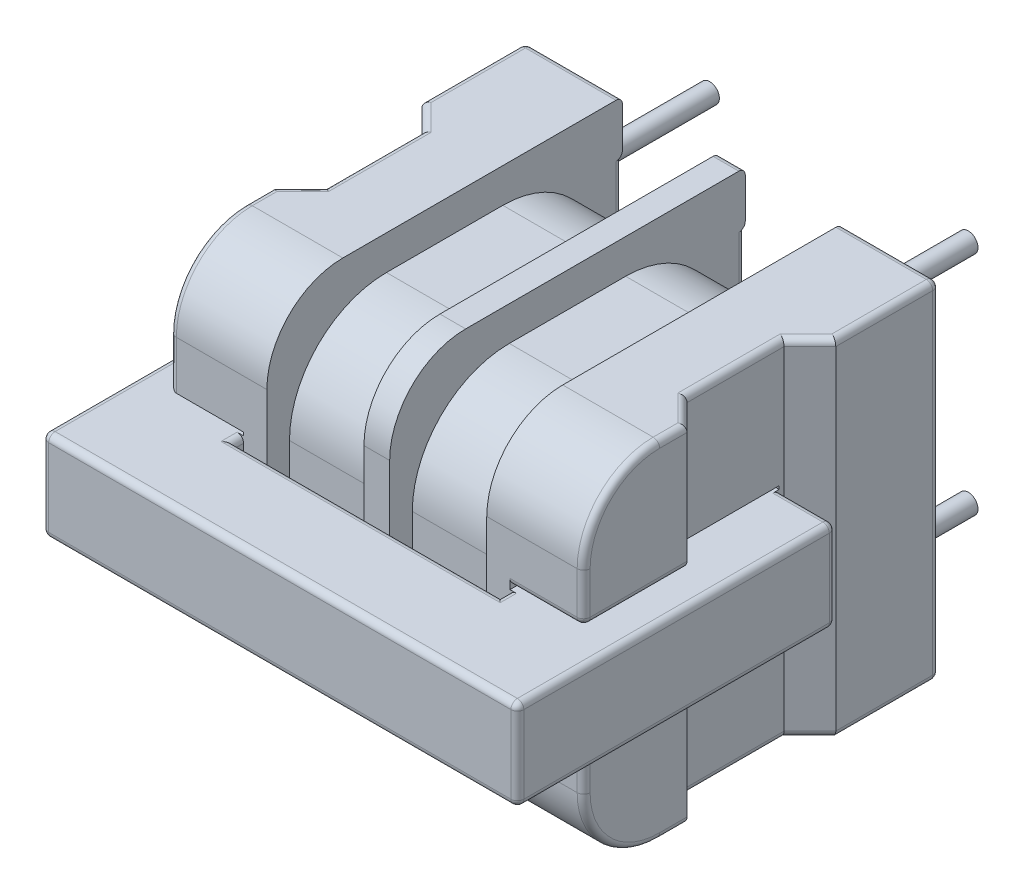
SolidWorks part; units mm, degrees
material "C (Graphite)"
ref_plane "Front Plane" through (0, 0, 0) normal (0, 0, 1) x (1, 0, 0)
ref_plane "Top Plane" through (0, 0, 0) normal (0, 1, 0) x (1, 0, 0)
ref_plane "Right Plane" through (0, 0, 0) normal (1, 0, 0) x (0, 0, -1)
sketch "Sketch1" plane through (0, 0, 0) normal (0, 0, 1) x (1, 0, 0)
  line L1 (-7.35, 5.35) -> (7.35, 5.35)
  line L2 (-7.35, 5.35) -> (-7.35, -5.35)
  line L3 (-7.35, -5.35) -> (7.35, -5.35)
  line L4 (7.35, 5.35) -> (7.35, -5.35)
  line L5 (-7.35, 5.35) -> (7.35, -5.35) construction
  line L6 (-7.35, -5.35) -> (7.35, 5.35) construction
  point P0 (0, 0)
  dimension "D1" = 10.7
  dimension "D2" = 14.7
extrude "Boss-Extrude1" add sketch "Sketch1" along normal blind 14
sketch "Sketch2" plane through (0, 0, 0) normal (1, 0, 0) x (0, 0, -1)
  line L0 (-5.5, 0) -> (0, 0) construction
  line L1 (-7, 4.5) -> (-4, 4.5)
  line L2 (-10, 1.5) -> (-10, -1.5)
  line L3 (-7, -4.5) -> (-4, -4.5)
  line L4 (-1, 1.5) -> (-1, -1.5)
  line L5 (-10, 4.5) -> (-1, -4.5) construction
  line L6 (-10, -4.5) -> (-1, 4.5) construction
  arc A0 (-10, -1.5) -> (-7, -4.5) centre (-7, -1.5) ccw
  arc A1 (-4, -4.5) -> (-1, -1.5) centre (-4, -1.5) ccw
  arc A2 (-4, 4.5) -> (-1, 1.5) centre (-4, 1.5) cw
  arc A3 (-7, 4.5) -> (-10, 1.5) centre (-7, 1.5) ccw
  point P0 (-5.5, 0)
  dimension "D1" = 3
  dimension "D3" = 5.5
  dimension "D2" = 9
sketch "Sketch3" plane through (0, 0, 0) normal (0, 1, 0) x (1, 0, 0)
  line L0 (-0.4, -10.8) -> (0.4, -10.8) construction
  line L1 (-3.4, -10.3) -> (-0.4, -10.3)
  line L2 (-3.4, -10.3) -> (-3.4, -11.3)
  line L3 (-3.4, -11.3) -> (-0.4, -11.3)
  line L4 (-0.4, -10.3) -> (-0.4, -11.3)
  line L5 (-3.4, -10.3) -> (-0.4, -11.3) construction
  line L6 (-3.4, -11.3) -> (-0.4, -10.3) construction
  line L7 (0.4, -10.3) -> (3.4, -10.3)
  line L8 (0.4, -10.3) -> (0.4, -11.3)
  line L9 (0.4, -11.3) -> (3.4, -11.3)
  line L10 (3.4, -10.3) -> (3.4, -11.3)
  line L11 (0.4, -10.3) -> (3.4, -11.3) construction
  line L12 (0.4, -11.3) -> (3.4, -10.3) construction
  line L13 (0, -10.382) -> (0, -10.8) construction
  line L14 (0, -10) -> (0, -1) construction
  line L17 (7.35, -14) -> (-7.35, -14) construction
  point P0 (-1.9, -10.8)
  point P5 (1.9, -10.8)
  dimension "D1" = 3
  dimension "D2" = 0.8
  dimension "D3" = 2.7
  dimension "D4" = 1
sweep "Cut-Sweep1" cut profiles "Sketch3" path "Sketch2"
sketch "Sketch4" plane through (0, 0, 0) normal (0, 0, 1) x (1, 0, 0)
  line L0 (7.35, -5.35) -> (7.35, 5.35) construction
  line L1 (-7.35, 5.35) -> (7.35, 5.35)
  line L2 (-7.35, 5.35) -> (-7.35, 1.4)
  line L3 (-7.35, 1.4) -> (7.35, 1.4)
  line L4 (7.35, 5.35) -> (7.35, 1.4)
  line L6 (-7.35, -5.35) -> (7.35, -5.35)
  line L7 (-7.35, -5.35) -> (-7.35, -1.4)
  line L8 (-7.35, -1.4) -> (7.35, -1.4)
  line L9 (7.35, -5.35) -> (7.35, -1.4)
  dimension "D1" = 2.8
extrude "Cut-Extrude1" cut sketch "Sketch4" against normal blind 3 from surface at 14 starting at face at (0, 0, 14)
fillet "Fillet1" radius 2.35 2 edges at (0, -5.35, 11) (0, 5.35, 11)
fillet "Fillet2" radius 0.2 12 edges at (-3.4, 0, 0) (-1.9, -3.078, 0) (-1.9, 3.078, 0) (-0.4, 0, 0) (0, -5.35, 0) (-7.35, 0, 0) (0, 5.35, 0) (7.35, 0, 0) (0.4, 0, 0) (1.9, -3.078, 0) (1.9, 3.078, 0) (3.4, 0, 0)
sketch "Sketch5" plane through (0, 0, 0) normal (0, 0, 1) x (1, 0, 0)
  line L0 (-3.4, 3.8033) -> (-3.4, 5.35) construction
  line L1 (-3.4, 4.2849) -> (-0.3962, 4.2849)
  line L2 (-3.4, 4.2849) -> (-3.4, 5.7963)
  line L3 (-3.4, 5.7963) -> (-0.3962, 5.7963)
  line L4 (-0.3962, 4.2849) -> (-0.3962, 5.7963)
  line L5 (0.4, 3.8033) -> (0.4, 5.35) construction
  line L6 (0.4, 4.2849) -> (3.4038, 4.2849)
  line L7 (0.4, 4.2849) -> (0.4, 5.7963)
  line L8 (0.4, 5.7963) -> (3.4038, 5.7963)
  line L9 (3.4038, 4.2849) -> (3.4038, 5.7963)
  line L10 (-3.4, -5.35) -> (-3.4, -3.8033) construction
  line L11 (-3.4, -4.418) -> (-0.3962, -4.418)
  line L12 (-3.4, -4.418) -> (-3.4, -6.0458)
  line L13 (-3.4, -6.0458) -> (-0.3962, -6.0458)
  line L14 (-0.3962, -4.418) -> (-0.3962, -6.0458)
  line L15 (-3.4, -4.8) -> (-3.4, -1.5) construction
  line L16 (0.4, -5.35) -> (0.4, -3.8033) construction
  line L17 (0.4, -4.418) -> (3.4038, -4.418)
  line L18 (0.4, -4.418) -> (0.4, -6.0458)
  line L19 (0.4, -6.0458) -> (3.4038, -6.0458)
  line L20 (3.4038, -4.418) -> (3.4038, -6.0458)
  line L21 (7.35, 1.4) -> (-7.35, 1.4) construction
  line L22 (-7.35, 5.35) -> (-6.4, 5.35)
  line L23 (-7.35, 5.35) -> (-7.35, 1.4)
  line L24 (-7.35, 1.4) -> (-6.4, 1.4)
  line L25 (-6.4, 5.35) -> (-6.4, 1.4)
  line L26 (-7.35, -5.35) -> (-6.4, -5.35)
  line L27 (-7.35, -5.35) -> (-7.35, -1.4)
  line L28 (-7.35, -1.4) -> (-6.4, -1.4)
  line L29 (-6.4, -5.35) -> (-6.4, -1.4)
  line L30 (7.35, 5.35) -> (6.4, 5.35)
  line L31 (7.35, 5.35) -> (7.35, 1.4)
  line L32 (7.35, 1.4) -> (6.4, 1.4)
  line L33 (6.4, 5.35) -> (6.4, 1.4)
  line L34 (7.35, -5.35) -> (6.4, -5.35)
  line L35 (7.35, -5.35) -> (7.35, -1.4)
  line L36 (7.35, -1.4) -> (6.4, -1.4)
  line L37 (6.4, -5.35) -> (6.4, -1.4)
  dimension "D1" = 12.8
extrude "Cut-Extrude2" cut sketch "Sketch5" along normal through all
sketch "Sketch6" plane through (0, 0, 0) normal (0, 0, 1) x (1, 0, 0)
  line L0 (0.4, -4.418) -> (0.4, -1.5) construction
  line L1 (-3.4, 5.35) -> (-0.4, 5.35)
  line L2 (-3.4, 5.35) -> (-3.4, 3)
  line L3 (-3.4, 3) -> (-0.4, 3)
  line L4 (-0.4, 5.35) -> (-0.4, 3)
  line L5 (0.4, 3) -> (3.4038, 3)
  line L6 (0.4, 3) -> (0.4, 5.35)
  line L7 (0.4, 5.35) -> (3.4038, 5.35)
  line L8 (3.4038, 3) -> (3.4038, 5.35)
  line L9 (-3.4, -5.35) -> (-0.4, -5.35)
  line L10 (-3.4, -5.35) -> (-3.4, -3)
  line L11 (-3.4, -3) -> (-0.4, -3)
  line L12 (-0.4, -5.35) -> (-0.4, -3)
  line L13 (0.4, -2.959) -> (3.4038, -2.959)
  line L14 (0.4, -2.959) -> (0.4, -5.35)
  line L15 (0.4, -5.35) -> (3.4038, -5.35)
  line L16 (3.4038, -2.959) -> (3.4038, -5.35)
extrude "Cut-Extrude3" cut sketch "Sketch6" along normal blind 1
sketch "Sketch7" plane through (0, 0, 0) normal (0, 0, 1) x (1, 0, 0)
  line L1 (-3.4, 3) -> (-0.3962, 3)
  line L2 (-3.4, 3) -> (-3.4, 5.35)
  line L3 (-3.4, 5.35) -> (-0.3962, 5.35)
  line L4 (-0.3962, 3) -> (-0.3962, 5.35)
  line L5 (0.4, 3) -> (3.4038, 3)
  line L6 (0.4, 3) -> (0.4, 5.35)
  line L7 (0.4, 5.35) -> (3.4038, 5.35)
  line L8 (3.4038, 3) -> (3.4038, 5.35)
  line L9 (-3.4, -3) -> (-0.3962, -3)
  line L10 (-3.4, -3) -> (-3.4, -5.35)
  line L11 (-3.4, -5.35) -> (-0.3962, -5.35)
  line L12 (-0.3962, -3) -> (-0.3962, -5.35)
  line L13 (0.4, -3) -> (3.4038, -3)
  line L14 (0.4, -3) -> (0.4, -5.35)
  line L15 (0.4, -5.35) -> (3.4038, -5.35)
  line L16 (3.4038, -3) -> (3.4038, -5.35)
extrude "Cut-Extrude4" cut sketch "Sketch7" against normal blind 1 from vertex
sketch "Sketch8" plane through (0, 0, 0) normal (0, 1, 0) x (1, 0, 0)
  line L0 (-6.4, -3.2) -> (-5.6, -4)
  line L1 (-6.4, -11) -> (-6.4, 0) construction
  line L2 (-5.6, -4) -> (-5.6, -7)
  line L3 (-5.6, -7) -> (-6.4, -7.8)
  line L4 (-6.4, -7.8) -> (-6.4, -3.2)
  line L5 (6.4, -3.2) -> (6.4, -7.8)
  line L6 (6.4, -8.65) -> (6.4, -0.2) construction
  line L7 (6.4, -7.8) -> (5.6, -7)
  line L8 (5.6, -7) -> (5.6, -4)
  line L9 (5.6, -4) -> (6.4, -3.2)
  line L10 (-5.6, -5.5) -> (-3.4, -5.5) construction
  line L11 (-3.4, -8.7704) -> (-3.4, -2.2296) construction
  line L13 (-3.4, -5.5) -> (5.6, -5.5) construction
  point P16 (-5.6, -5.5)
  dimension "D1" = 4.6
  dimension "D2" = 3
extrude "Cut-Extrude5" cut sketch "Sketch8" along normal through all from vertex
sketch "Sketch9" plane through (0, 0, 0) normal (0, 1, 0) x (1, 0, 0)
  line L0 (-6.4, -3.2) -> (-5.6, -4)
  line L1 (-5.6, -4) -> (-5.6, -7)
  line L2 (-5.6, -7) -> (-6.4, -7.8)
  line L3 (-6.4, -7.8) -> (-6.4, -3.2)
  line L4 (6.4, -3.2) -> (5.6, -4)
  line L5 (5.6, -4) -> (5.6, -7)
  line L6 (5.6, -7) -> (6.4, -7.8)
  line L7 (6.4, -7.8) -> (6.4, -3.2)
extrude "Cut-Extrude6" cut sketch "Sketch9" against normal through all from vertex
sketch "Sketch10" plane through (0, 0, 0) normal (0, 1, 0) x (1, 0, 0)
  line L0 (-3.4, -11) -> (-6.4, -11) construction
  line L1 (-4.12, -11) -> (4.12, -11)
  line L2 (-4.12, -11) -> (-4.12, -11.3)
  line L3 (-4.12, -11.3) -> (4.12, -11.3)
  line L4 (4.12, -11) -> (4.12, -11.3)
  line L5 (6.4, -11) -> (3.4, -11) construction
  line L6 (-0.4, -11.3) -> (-3.4, -11.3) construction
  line L7 (-4.12, -11) -> (-6.4, -11) construction
  line L8 (4.12, -11) -> (6.4, -11) construction
  line L9 (-6.4, 0) -> (-6.4, -3.2)
  line L10 (-6.4, -3.2) -> (-5.6, -4)
  line L11 (-5.6, -4) -> (-5.6, -4.15)
  line L12 (-5.6, -7) -> (-5.6, -4) construction
  line L13 (-5.6, -4.15) -> (-7.35, -4.15)
  line L14 (-7.35, -0.2) -> (-7.35, -14) construction
  line L15 (-7.35, -4.15) -> (-7.35, 0)
  line L16 (-7.35, 0) -> (-6.4, 0)
  line L17 (6.4, 0) -> (6.4, -3.2)
  line L18 (6.4, -3.2) -> (5.6, -4)
  line L19 (5.6, -4) -> (5.6, -4.15)
  line L20 (5.6, -4) -> (5.6, -7) construction
  line L21 (5.6, -4.15) -> (7.35, -4.15)
  line L22 (7.35, -0.2) -> (7.35, -14) construction
  line L23 (7.35, -4.15) -> (7.35, 0)
  line L24 (7.35, 0) -> (6.4, 0)
  line L25 (-5.6, -7) -> (-5.6, -6.85) construction
  line L26 (-5.6, -6.85) -> (-5.6, -4.15) construction
  line L27 (5.6, -7) -> (5.6, -6.85) construction
  line L28 (5.6, -4) -> (5.6, -7) construction
  line L29 (5.6, -6.85) -> (5.6, -4.15) construction
  dimension "D1" = 8.24
  dimension "D2" = 2.7
extrude "Cut-Extrude7" cut sketch "Sketch10" against normal through all and the other way through all
sketch "Sketch11" plane through (0, 0, 0) normal (0, 0, 1) x (1, 0, 0)
  line L0 (-4.12, -1.4) -> (-4.12, 1.4) construction
  line L1 (-7.35, 1.4) -> (-4.12, 1.4)
  line L2 (-7.35, 1.4) -> (-7.35, 1.5)
  line L3 (-7.35, 1.5) -> (-4.12, 1.5)
  line L4 (-4.12, 1.4) -> (-4.12, 1.5)
  line L5 (-7.35, -1.4) -> (-4.12, -1.4)
  line L6 (-7.35, -1.4) -> (-7.35, -1.5)
  line L7 (-7.35, -1.5) -> (-4.12, -1.5)
  line L8 (-4.12, -1.4) -> (-4.12, -1.5)
  line L9 (7.35, 1.4) -> (4.12, 1.4)
  line L10 (7.35, 1.4) -> (7.35, 1.5)
  line L11 (7.35, 1.5) -> (4.12, 1.5)
  line L12 (4.12, 1.4) -> (4.12, 1.5)
  line L13 (7.35, -1.4) -> (4.12, -1.4)
  line L14 (7.35, -1.4) -> (7.35, -1.5)
  line L15 (7.35, -1.5) -> (4.12, -1.5)
  line L16 (4.12, -1.4) -> (4.12, -1.5)
  dimension "D1" = 0.1
extrude "Cut-Extrude8" cut sketch "Sketch11" along normal up to vertex from vertex
fillet "Fillet3" radius 0.2 62 edges at (-6.4, 2.25, 11) (-6, 1.5, 7.4) (-6.4, 1.5, 9.4) (-6, -1.5, 7.4) (-6.4, -1.5, 9.4) (6, 1.5, 7.4) (6.4, 1.5, 9.4) (6, -1.5, 7.4) (6.4, -2.25, 11) (6.4, -1.5, 9.4) (0, 1.4, 11.3) (-7.35, 0, 14) (0, 1.4, 14) (0, -1.4, 11.3) (7.35, 0, 14) (0, -1.4, 14) (-6.4, 5.35, 8.225) (-6.4, 0, 0) (-6.4, 5.2914, 0.0586) (-6.4, 4.6617, 10.3117) (-6.4, -2.25, 11) (-6.4, -5.35, 8.225) (-6.4, -5.2914, 0.0586) (-6.4, -4.6617, 10.3117) (6.4, 2.25, 11) (6.4, 5.35, 8.225) (6.4, 5.2914, 0.0586) (6.4, 0, 0) (6.4, 4.6617, 10.3117) (6.4, -5.35, 8.225) (6.4, -5.2914, 0.0586) (6.4, -4.6617, 10.3117) (-6.4, 5.35, 1.7) (-6, 5.35, 7.4) (-5.6, 5.35, 5.5) (-6, 5.35, 3.6) (6.4, 5.35, 1.7) (6, 5.35, 3.6) (5.6, 5.35, 5.5) (6, 5.35, 7.4) (-6.4, -5.35, 1.7) (-6, -5.35, 3.6) (-5.6, -5.35, 5.5) (-6, -5.35, 7.4) (6.4, -5.35, 1.7) (6, -5.35, 7.4) (5.6, -5.35, 5.5) (6, -5.35, 3.6) (-4.12, -1.4, 11.15) (4.12, -1.4, 11.15) (-4.12, 1.4, 11.15) (4.12, 1.4, 11.15) (-7.35, -1.4, 9.075) (-7.35, 1.4, 9.075) (-6.475, 1.4, 4.15) (-6.475, -1.4, 4.15) (-7.35, 0, 4.15) (7.35, -1.4, 9.075) (7.35, 1.4, 9.075) (6.475, 1.4, 4.15) (6.475, -1.4, 4.15) (7.35, 0, 4.15)
fillet "Fillet4" radius 3 8 edges at (-1.9, -4.418, 2.4589) (1.9, -4.418, 2.4589) (1.9, -4.418, 8.5411) (-1.9, -4.418, 8.5411) (1.9, 4.2849, 2.2296) (-1.9, 4.2849, 2.2296) (1.9, 4.2849, 8.7704) (-1.9, 4.2849, 8.7704)
sketch "Sketch16" plane through (0, 0, 0) normal (0, 0, 1) x (1, 0, 0)
  line L0 (0, 0) -> (4, 3.5) construction
  line L1 (4, 3.5) -> (-4, 3.5) construction
  line L2 (-4, 3.5) -> (-4, -3.5) construction
  line L3 (-4, -3.5) -> (0, 0) construction
  line L4 (0, 0) -> (4, -3.5) construction
  line L5 (4, -3.5) -> (4, 3.5) construction
  circle A0 centre (-4, 3.5) radius 0.3
  circle A1 centre (4, 3.5) radius 0.3
  circle A2 centre (4, -3.5) radius 0.3
  circle A3 centre (-4, -3.5) radius 0.3
  dimension "D3" = 0.6
  dimension "D1" = 8
  dimension "D2" = 7
extrude "Boss-Extrude2" add sketch "Sketch16" along normal blind 1 and the other way blind 3.3
